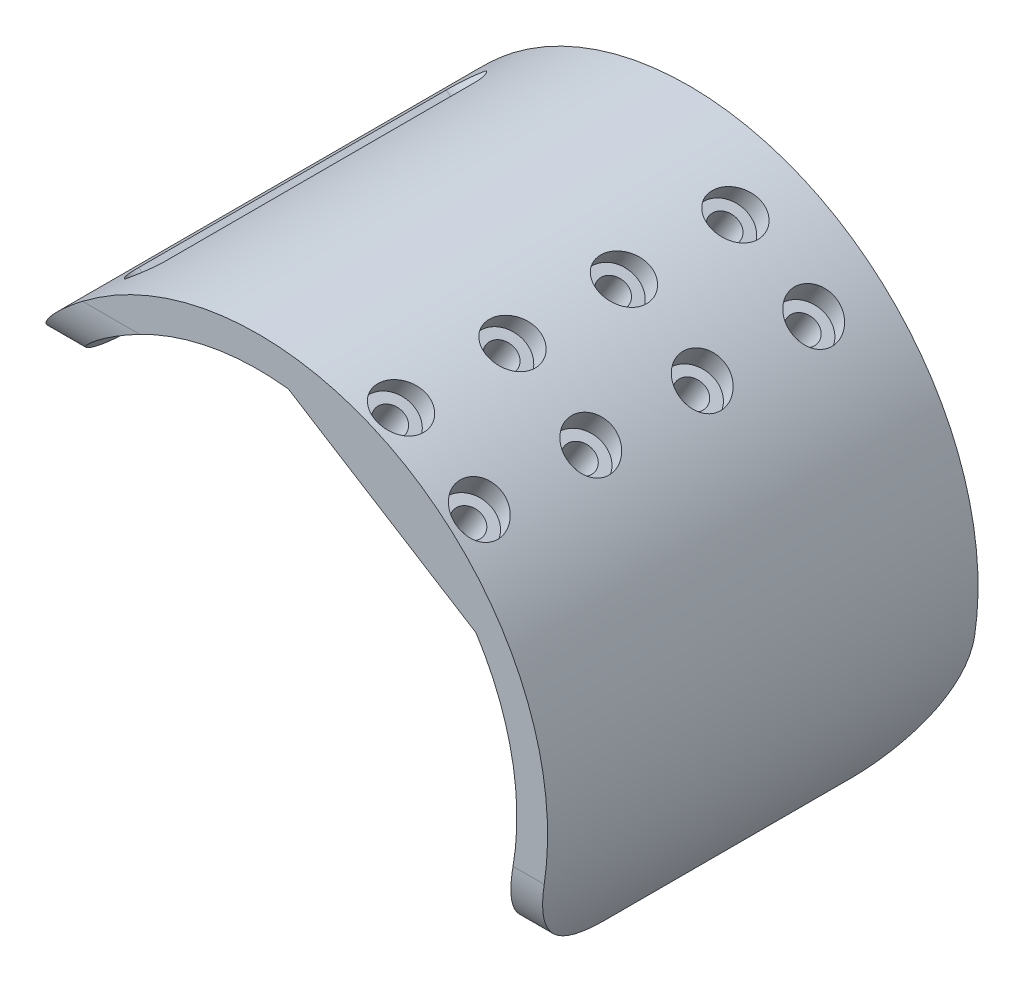
SolidWorks part; units mm, degrees
ref_plane "Plan de face" through (0, 0, 0) normal (0, 0, 1) x (1, 0, 0)
ref_plane "Plan de dessus" through (0, 0, 0) normal (0, 1, 0) x (1, 0, 0)
ref_plane "Plan de droite" through (0, 0, 0) normal (1, 0, 0) x (0, 0, -1)
sketch "Esquisse2" plane through (0, 0, 15) normal (0, 0, 1) x (1, 0, 0)
  line L0 (-73.5002, 11.2174) -> (-67.7143, 11.2174)
  line L1 (3.5979, -33.3527) -> (9.3691, -33.3527)
  line L2 (-27.235, 30.6113) -> (3.2925, 11.5317)
  line L3 (-44.7779, -3.1178) -> (-37.2727, -7.8086) construction
  line L4 (-26.8437, -14.3267) -> (-19.3384, -19.0175) construction
  line L5 (-27.235, 30.6113) -> (3.2925, 11.5317)
  line L6 (-27.235, 30.6113) -> (-25.0898, 34.0436)
  line L7 (3.2925, 11.5317) -> (5.4377, 14.9639)
  line L8 (-25.0898, 34.0436) -> (5.4377, 14.9639)
  arc A0 (3.5979, -33.3527) -> (-67.7143, 11.2174) centre (-32.1112, -11.1524) ccw
  arc A1 (9.3691, -33.3527) -> (-73.5002, 11.2174) centre (-32.1112, -11.1524) ccw
  dimension "D1" = 5
  dimension "D2" = 0
  dimension "D3" = 0
extrude "Boss.-Extru.1" add sketch "Esquisse2" along normal blind 70 from surface contours L1 A1 L0 A0 | L5 L6 L8 L7
sketch "Esquisse3" plane through (6.1076, 9.7722, 0) normal (-0.53, -0.848, 0) x (0.848, -0.53, 0)
  line L0 (-28.8193, -100) -> (-28.8193, -170) construction
  line L1 (-39.3192, -100) -> (-3.3197, -100) construction
  line L2 (-39.3192, -170) -> (-3.3197, -170) construction
  line L3 (-28.8193, -170) -> (-13.8196, -170) construction
  line L4 (-13.8196, -170) -> (-13.8196, -100) construction
  line L5 (-3.3197, -100) -> (-3.3197, -170) construction
  circle A0 centre (-28.8193, -105) radius 2.3
  circle A1 centre (-13.8196, -105) radius 2.3
  circle A2 centre (-13.8196, -123.125) radius 2.3
  circle A3 centre (-28.8193, -141.25) radius 2.3
  circle A4 centre (-28.8193, -123.125) radius 2.3
  circle A5 centre (-13.8196, -141.25) radius 2.3
  circle A6 centre (-13.8196, -159.375) radius 2.3
  circle A7 centre (-28.8193, -159.375) radius 2.3
  point P34 (0, 0)
  point P35 (0, 0)
  point P36 (0, 0)
  point P37 (0, 0)
  point P38 (0, 0)
  point P39 (0, 0)
  point P40 (0, 0)
  dimension "D1" = 4.6
  dimension "D2" = 18.125
  dimension "D3" = 18.125
  dimension "D4" = 18.125
  dimension "D5" = 18.125
  dimension "D6" = 18.125
  dimension "D7" = 18.125
  dimension "D8" = 5
  dimension "D9" = 5
  dimension "D10" = 14.9997
  dimension "D11" = 10.4999
extrude "Enlèv. mat.-Extru.1" cut sketch "Esquisse3" against normal through all
sketch "Esquisse4" plane through (6.1076, 9.7722, 0) normal (-0.53, -0.848, 0) x (0.848, -0.53, 0)
  circle A1 centre (-13.8196, -105) radius 4
  circle A2 centre (-13.8196, -123.125) radius 4
  circle A3 centre (-13.8196, -141.25) radius 4
  circle A4 centre (-13.8196, -159.375) radius 4
  circle A5 centre (-28.8193, -159.375) radius 4
  circle A6 centre (-28.8193, -141.25) radius 4
  circle A7 centre (-28.8193, -123.125) radius 4
  circle A8 centre (-28.8193, -105) radius 4
  dimension "D1" = 8
extrude "Enlèv. mat.-Extru.3" cut sketch "Esquisse4" along normal blind 4 from offset 9 offset against normal yes
sketch "Esquisse5" plane through (-30.7986, 19.2491, 0) normal (-0.848, 0.53, 0) x (0, 0, 1)
  line L0 (-165, -5.9761) -> (-105, -5.9761)
  line L1 (-165, -5.9761) -> (-165, -10.9761)
  line L2 (-105, -5.9761) -> (-105, -10.9761)
  line L3 (-165, -10.9761) -> (-105, -10.9761)
  line L4 (-168, 11.5239) -> (-17, 11.5239) construction
  line L5 (-170, 20.5713) -> (-170, -29.4427) construction
  dimension "D1" = 17.5
  dimension "D2" = 22.5
  dimension "D3" = 60
  dimension "D4" = 5
extrude "Enlèv. mat.-Extru.4" cut sketch "Esquisse5" along normal blind 50
fillet "Congé1" radius 5 4 edges at (-54.7667, 27.1819, -105) (-54.7667, 27.1819, -165) (-59.3032, 24.1209, -105) (-59.3032, 24.1209, -165)
fillet "Congé2" radius 15 4 edges at (-70.6073, 11.2174, -170) (-70.6073, 11.2174, -100) (6.4835, -33.3527, -170) (6.4835, -33.3527, -100)
